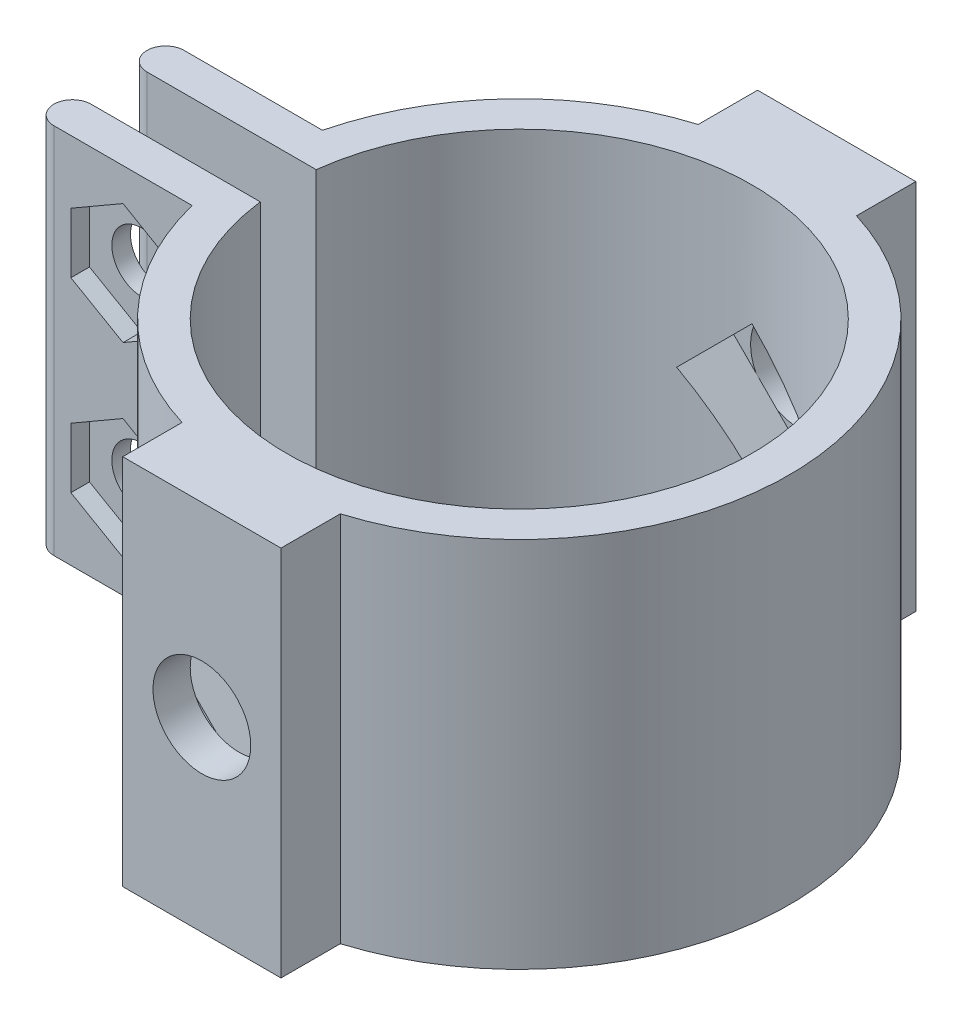
SolidWorks part; units mm, degrees
ref_plane "Front Plane" through (0, 0, 0) normal (0, 0, 1) x (1, 0, 0)
ref_plane "Top Plane" through (0, 0, 0) normal (0, 1, 0) x (1, 0, 0)
ref_plane "Right Plane" through (0, 0, 0) normal (1, 0, 0) x (0, 0, -1)
sketch "Sketch1" plane through (0, 0, 0) normal (0, 1, 0) x (1, 0, 0)
  line L0 (-12.5, -17.5) -> (-12.5, 17.5) construction
  line L7 (-12.4097, -1.5) -> (-12.5, -1.5)
  line L8 (-12.4097, 1.5) -> (-12.5, 1.5)
  line L9 (-12.5, -1.5) -> (-21.5, -1.5)
  line L10 (-12.5, 1.5) -> (-21.5, 1.5)
  line L11 (-14.0712, 3.5) -> (-21.5, 3.5)
  line L12 (-14.0712, 3.5) -> (-14.0712, 3.5)
  line L13 (-14.0712, -3.5) -> (-14.0712, -3.5)
  line L14 (-14.0712, -3.5) -> (-21.5, -3.5)
  line L16 (-4.25, -13.8632) -> (-4.25, -14.5)
  line L17 (4.25, -14.5) -> (4.25, -13.8632)
  line L18 (0, 0) -> (10.0696, 0) construction
  line L19 (-4.25, -14.5) -> (4.25, -14.5) construction
  line L20 (-4.25, -14.5) -> (-4.25, -17.05)
  line L21 (-4.25, -17.05) -> (4.25, -17.05)
  line L22 (4.25, -14.5) -> (4.25, -17.05)
  line L23 (4.25, 14.5) -> (4.25, 17.05)
  line L24 (-4.25, 17.05) -> (4.25, 17.05)
  line L25 (-4.25, 14.5) -> (-4.25, 17.05)
  line L26 (-4.25, 14.5) -> (4.25, 14.5) construction
  line L27 (4.25, 14.5) -> (4.25, 13.8632)
  line L28 (-4.25, 13.8632) -> (-4.25, 14.5)
  circle A0 centre (0, 0) radius 12.5 construction
  arc A1 (-12.4097, 1.5) -> (-12.4097, -1.5) centre (0, 0) cw
  arc A2 (-14.0712, 3.5) -> (-14.0712, -3.5) centre (0, 0) cw
  arc A3 (-21.5, 1.5) -> (-21.5, 3.5) centre (-21.5, 2.5) cw
  arc A4 (-21.5, -1.5) -> (-21.5, -3.5) centre (-21.5, -2.5) ccw
  point P0 (0, 0)
  point P15 (-12.5, 0)
  point P32 (0, 14.5)
  point P40 (0, -14.5)
  dimension "D3" = 25
  dimension "D1" = 2.55
  dimension "D4" = 9
  dimension "D6" = 3
  dimension "D7" = 8.5
  dimension "D5" = 2
extrude "Boss-Extrude1" add sketch "Sketch1" along normal mid plane 20 contours L9 A4 L14 A2 L11 A3 L10 L8 A1 L7 | L17 A2 L16 L20 L21 L22 | L28 A2 L27 L23 L24 L25 region at (12.9701, 0, 0) region at (0, 0, 15.6633) region at (0, 0, -15.6633)
sketch "Sketch7" plane through (0, 0, 17.05) normal (0, 0, 1) x (1, 0, 0)
  line L1 (0, 3.5355) -> (-3.5355, 0)
  line L2 (-3.5355, 0) -> (0, -3.5355)
  line L3 (0, -3.5355) -> (3.5355, 0)
  line L4 (3.5355, 0) -> (0, 3.5355)
  circle A0 centre (0, 0) radius 2.5 construction
  circle A1 centre (0, 0) radius 2.5 construction
  line M1 (-4.25, -10) -> (4.25, -10)
  dimension "D1" = 5
extrude "Cut-Extrude10" cut sketch "Sketch7" against normal up to surface (3.0604 mm away) from offset 2 contours L3 L4 L1 L2 M1 region at (0, 0, 17.05) up to face at (0.0452, 0, 0) offset against normal yes
sketch "Sketch8" plane through (0, 0, 17.05) normal (0, 0, 1) x (1, 0, 0)
  line L4 (0, 3.5355) -> (-3.5355, 0)
  line L5 (-3.5355, 0) -> (0, -3.5355)
  line L6 (0, -3.5355) -> (3.5355, 0)
  line L7 (3.5355, 0) -> (0, 3.5355)
  line L8 (0, 3.5355) -> (-3.5355, 0) construction
  line L9 (-3.5355, 0) -> (0, -3.5355) construction
  line L10 (0, -3.5355) -> (3.5355, 0) construction
  line L11 (3.5355, 0) -> (0, 3.5355) construction
  circle A0 centre (0, 0) radius 2.625
  dimension "D2" = 5.25
  dimension "D1" = 0
extrude "Cut-Extrude11" cut sketch "Sketch8" against normal up to surface (2 mm away) up to face at (0, 0, 15.05)
mirror "Mirror2" about plane through (0, 0, 0) normal (0, 0, 1) of "Cut-Extrude11", "Cut-Extrude10"
sketch "Sketch9" plane through (0, 0, 3.5) normal (0, 0, 1) x (1, 0, 0)
  line L0 (-14.0712, 10) -> (-21.5, 10) construction
  line L2 (-17.7856, -5) -> (-17.7856, -10) construction
  line L3 (-14.0712, -10) -> (-21.5, -10) construction
  line L4 (-17.7856, 5) -> (-17.7856, 10) construction
  line L6 (-17.7856, 8.2332) -> (-20.5856, 6.6166)
  line L7 (-20.5856, 6.6166) -> (-20.5856, 3.3834)
  line L8 (-20.5856, 3.3834) -> (-17.7856, 1.7668)
  line L9 (-17.7856, 1.7668) -> (-14.9856, 3.3834)
  line L10 (-14.9856, 3.3834) -> (-14.9856, 6.6166)
  line L11 (-14.9856, 6.6166) -> (-17.7856, 8.2332)
  line L12 (-17.7856, -1.7668) -> (-20.5856, -3.3834)
  line L13 (-20.5856, -3.3834) -> (-20.5856, -6.6166)
  line L14 (-20.5856, -6.6166) -> (-17.7856, -8.2332)
  line L15 (-17.7856, -8.2332) -> (-14.9856, -6.6166)
  line L16 (-14.9856, -6.6166) -> (-14.9856, -3.3834)
  line L17 (-14.9856, -3.3834) -> (-17.7856, -1.7668)
  circle A0 centre (-17.7856, 5) radius 2.8 construction
  circle A1 centre (-17.7856, -5) radius 2.8 construction
  point P0 (-17.7856, 10)
  point P1 (-17.7856, 5)
  point P4 (-17.7856, -5)
  point P7 (0, 0)
  point P26 (-17.7856, -1.798)
  point P27 (-17.7856, 5.7429)
  point P28 (-17.7856, -4.8841)
  point P29 (-17.7856, 5.3403)
  point P30 (-17.7856, -4.6694)
  point P31 (-17.7856, 5.5013)
  dimension "D1" = 5.6
  dimension "D2" = 5
extrude "Cut-Extrude12" cut sketch "Sketch9" against normal blind 1
sketch "Sketch10" plane through (0, 0, 2.5) normal (0, 0, 1) x (1, 0, 0)
  line L6 (-17.7856, -1.7668) -> (-20.5856, -3.3834)
  line L7 (-20.5856, -3.3834) -> (-20.5856, -6.6166)
  line L8 (-20.5856, -6.6166) -> (-17.7856, -8.2332)
  line L9 (-17.7856, -8.2332) -> (-14.9856, -6.6166)
  line L10 (-14.9856, -6.6166) -> (-14.9856, -3.3834)
  line L11 (-14.9856, -3.3834) -> (-17.7856, -1.7668)
  line L12 (-17.7856, -1.7668) -> (-20.5856, -3.3834)
  line L13 (-20.5856, -3.3834) -> (-20.5856, -6.6166)
  line L14 (-20.5856, -6.6166) -> (-17.7856, -8.2332)
  line L15 (-17.7856, -8.2332) -> (-14.9856, -6.6166)
  line L16 (-14.9856, -6.6166) -> (-14.9856, -3.3834)
  line L17 (-14.9856, -3.3834) -> (-17.7856, -1.7668)
  line L18 (-14.9856, 3.3834) -> (-14.9856, 6.6166)
  line L19 (-14.9856, 6.6166) -> (-17.7856, 8.2332)
  line L20 (-17.7856, 8.2332) -> (-20.5856, 6.6166)
  line L21 (-20.5856, 6.6166) -> (-20.5856, 3.3834)
  line L22 (-20.5856, 3.3834) -> (-17.7856, 1.7668)
  line L23 (-17.7856, 1.7668) -> (-14.9856, 3.3834)
  line L24 (-14.9856, 3.3834) -> (-14.9856, 6.6166)
  line L25 (-14.9856, 6.6166) -> (-17.7856, 8.2332)
  line L26 (-17.7856, 8.2332) -> (-20.5856, 6.6166)
  line L27 (-20.5856, 6.6166) -> (-20.5856, 3.3834)
  line L28 (-20.5856, 3.3834) -> (-17.7856, 1.7668)
  line L29 (-17.7856, 1.7668) -> (-14.9856, 3.3834)
  circle A0 centre (-17.7856, 5) radius 1.6
  circle A1 centre (-17.7856, -5) radius 1.6
  point P6 (-17.7856, 5)
  point P10 (-17.7856, -5)
  point P12 (-14.9856, -5)
  point P14 (-14.9856, 5)
  dimension "D3" = 3.2
  dimension "D1" = 0
  dimension "D2" = 0
extrude "Cut-Extrude13" cut sketch "Sketch10" against normal up to surface (6 mm away) contours A0 | A1 region at (-17.7856, 5, 2.5) region at (-17.7856, -5, 2.5) up to face at (-17.7856, 0, -3.5)
equation "\"a\"= 1"
equation "\"b\"= 1"
equation "\"c\"= 1"
equation "\"d\"= 1"
equation "\"e\"= 1"
equation "\"x\"= 1"
equation "\"y\"= 1"
equation "\"z\"= 1"
